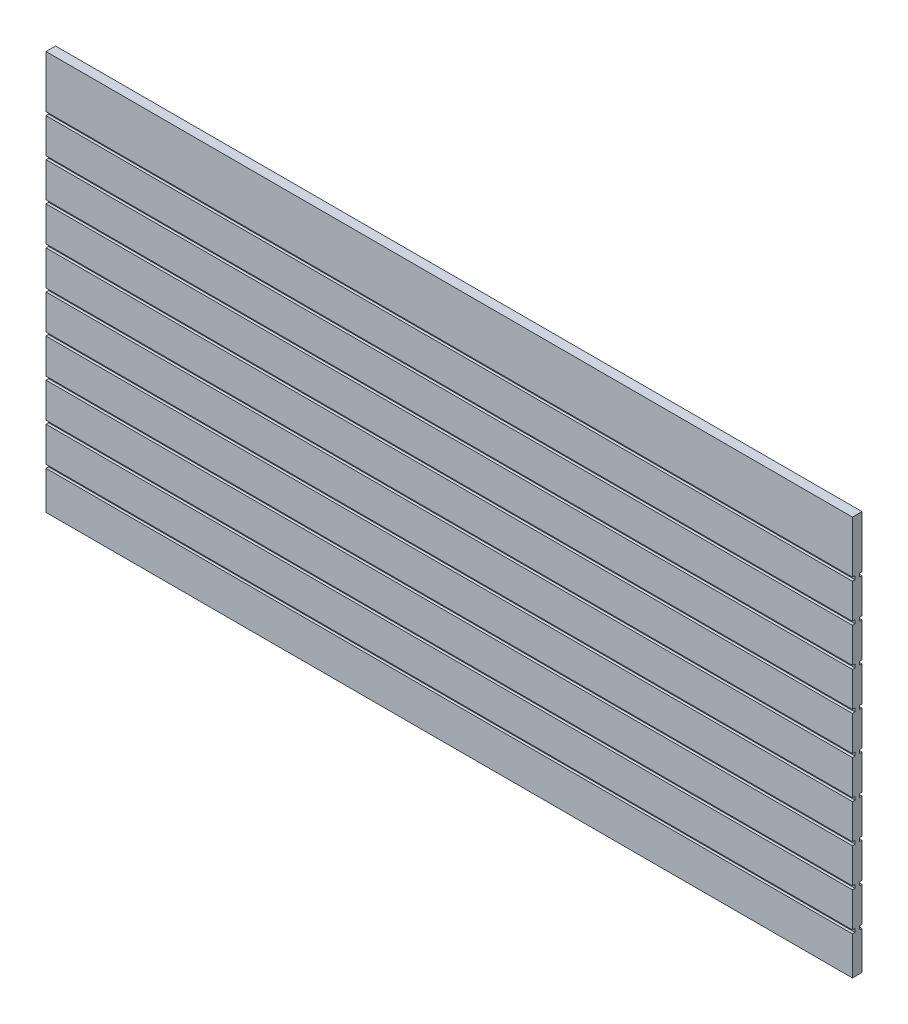
SolidWorks part; units mm, degrees
ref_plane "Front Plane" through (0, 0, 0) normal (0, 0, 1) x (1, 0, 0)
ref_plane "Top Plane" through (0, 0, 0) normal (0, 1, 0) x (1, 0, 0)
ref_plane "Right Plane" through (0, 0, 0) normal (1, 0, 0) x (0, 0, -1)
sketch "Sketch1" plane through (0, 0, 0) normal (0, 0, 1) x (1, 0, 0)
  line L1 (-737.6583, -365.125) -> (737.6583, -365.125)
  line L2 (-737.6583, -365.125) -> (-737.6583, 365.125)
  line L3 (-737.6583, 365.125) -> (737.6583, 365.125)
  line L4 (737.6583, -365.125) -> (737.6583, 365.125)
  line L5 (-737.6583, -365.125) -> (737.6583, 365.125) construction
  line L6 (-737.6583, 365.125) -> (737.6583, -365.125) construction
  point P0 (0, 0)
  dimension "D1" = 730.25
extrude "Boss-Extrude1" add sketch "Sketch1" along normal blind 8.7376 and the other way blind 8.7376
sketch "Sketch2" plane through (0, 0, 8.7376) normal (0, 0, 1) x (1, 0, 0)
  line L0 (-737.6583, 365.125) -> (-737.6583, -365.125) construction
  line L1 (737.6583, -365.125) -> (737.6583, 365.125) construction
  line L2 (-737.6583, -295.275) -> (737.6583, -295.275)
  line L3 (-737.6583, -295.275) -> (-737.6583, -288.925)
  line L4 (-737.6583, -288.925) -> (737.6583, -288.925)
  line L5 (737.6583, -295.275) -> (737.6583, -288.925)
  line L6 (-737.6583, -365.125) -> (737.6583, -365.125) construction
  line L7 (-737.6583, -225.425) -> (737.6583, -225.425)
  line L8 (-737.6583, -225.425) -> (-737.6583, -219.075)
  line L9 (-737.6583, -219.075) -> (737.6583, -219.075)
  line L10 (737.6583, -225.425) -> (737.6583, -219.075)
  line L11 (-737.6583, -155.575) -> (737.6583, -155.575)
  line L12 (-737.6583, -155.575) -> (-737.6583, -149.225)
  line L13 (-737.6583, -149.225) -> (737.6583, -149.225)
  line L14 (737.6583, -155.575) -> (737.6583, -149.225)
  line L15 (-737.6583, -85.725) -> (737.6583, -85.725)
  line L16 (-737.6583, -85.725) -> (-737.6583, -79.375)
  line L17 (-737.6583, -79.375) -> (737.6583, -79.375)
  line L18 (737.6583, -85.725) -> (737.6583, -79.375)
  line L19 (-737.6583, -15.875) -> (737.6583, -15.875)
  line L20 (-737.6583, -15.875) -> (-737.6583, -9.525)
  line L21 (-737.6583, -9.525) -> (737.6583, -9.525)
  line L22 (737.6583, -15.875) -> (737.6583, -9.525)
  line L23 (-737.6583, 53.975) -> (737.6583, 53.975)
  line L24 (-737.6583, 53.975) -> (-737.6583, 60.325)
  line L25 (-737.6583, 60.325) -> (737.6583, 60.325)
  line L26 (737.6583, 53.975) -> (737.6583, 60.325)
  line L27 (-737.6583, 123.825) -> (737.6583, 123.825)
  line L28 (-737.6583, 123.825) -> (-737.6583, 130.175)
  line L29 (-737.6583, 130.175) -> (737.6583, 130.175)
  line L30 (737.6583, 123.825) -> (737.6583, 130.175)
  line L31 (-737.6583, 193.675) -> (737.6583, 193.675)
  line L32 (-737.6583, 193.675) -> (-737.6583, 200.025)
  line L33 (-737.6583, 200.025) -> (737.6583, 200.025)
  line L34 (737.6583, 193.675) -> (737.6583, 200.025)
  line L35 (-737.6583, 263.525) -> (737.6583, 263.525)
  line L36 (-737.6583, 263.525) -> (-737.6583, 269.875)
  line L37 (-737.6583, 269.875) -> (737.6583, 269.875)
  line L38 (737.6583, 263.525) -> (737.6583, 269.875)
  dimension "D1" = 6.35
  dimension "D2" = 69.85
  dimension "D3" = 9
extrude "Cut-Extrude1" cut sketch "Sketch2" against normal blind 4.7625
mirror "Mirror1" about plane through (0, 0, 0) normal (0, 0, 1) of "Cut-Extrude1"
